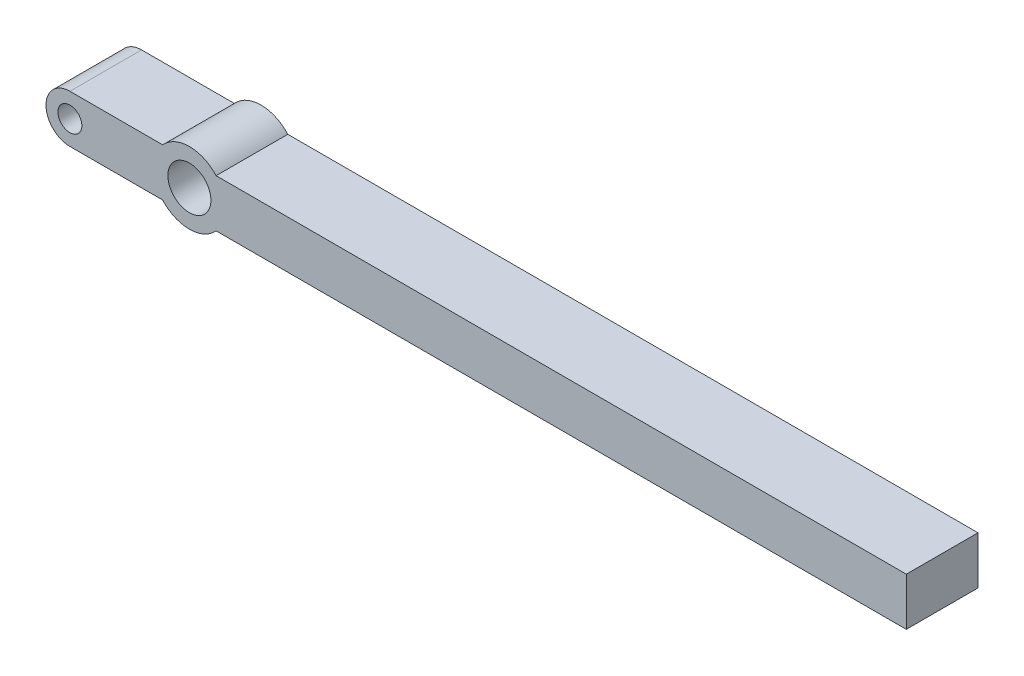
SolidWorks part; units mm, degrees
ref_plane "Front Plane" through (0, 0, 0) normal (0, 0, 1) x (1, 0, 0)
ref_plane "Top Plane" through (0, 0, 0) normal (0, 1, 0) x (1, 0, 0)
ref_plane "Right Plane" through (0, 0, 0) normal (1, 0, 0) x (0, 0, -1)
sketch "Sketch1" plane through (0, 0, 0) normal (0, 0, 1) x (1, 0, 0)
  line L0 (-6.6245, 33.7805) -> (282.1951, 33.7805)
  line L1 (-67.8049, 33.7805) -> (-28.9852, 33.7805)
  line L3 (-67.8049, 13.7805) -> (-28.9852, 13.7805)
  line L4 (282.1951, 33.7805) -> (282.1951, 13.7805)
  line L5 (-62.8049, 23.7805) -> (-57.8049, 23.7805)
  line L6 (-6.6245, 13.7805) -> (282.1951, 13.7805)
  circle A0 centre (-17.8049, 23.7805) radius 15
  circle A1 centre (-17.8049, 23.7805) radius 9
  circle A2 centre (-67.8049, 23.7805) radius 5
  circle A3 centre (-67.8049, 23.7805) radius 10
  dimension "D4" = 30
  dimension "D5" = 18
  dimension "D6" = 10
  dimension "D1" = 350
  dimension "D7" = 50
extrude "Boss-Extrude1" add sketch "Sketch1" along normal blind 15 and the other way blind 15 contours A0 L6 L4 L0 | A0 A1 | A3 L3 A0 L1 | A3 A2 region at (139.0928, 23.7805, 0) region at (-4.1886, 28.9814, 0) region at (-45.8437, 23.7805, 0) region at (-60.9338, 30.6516, 0)
